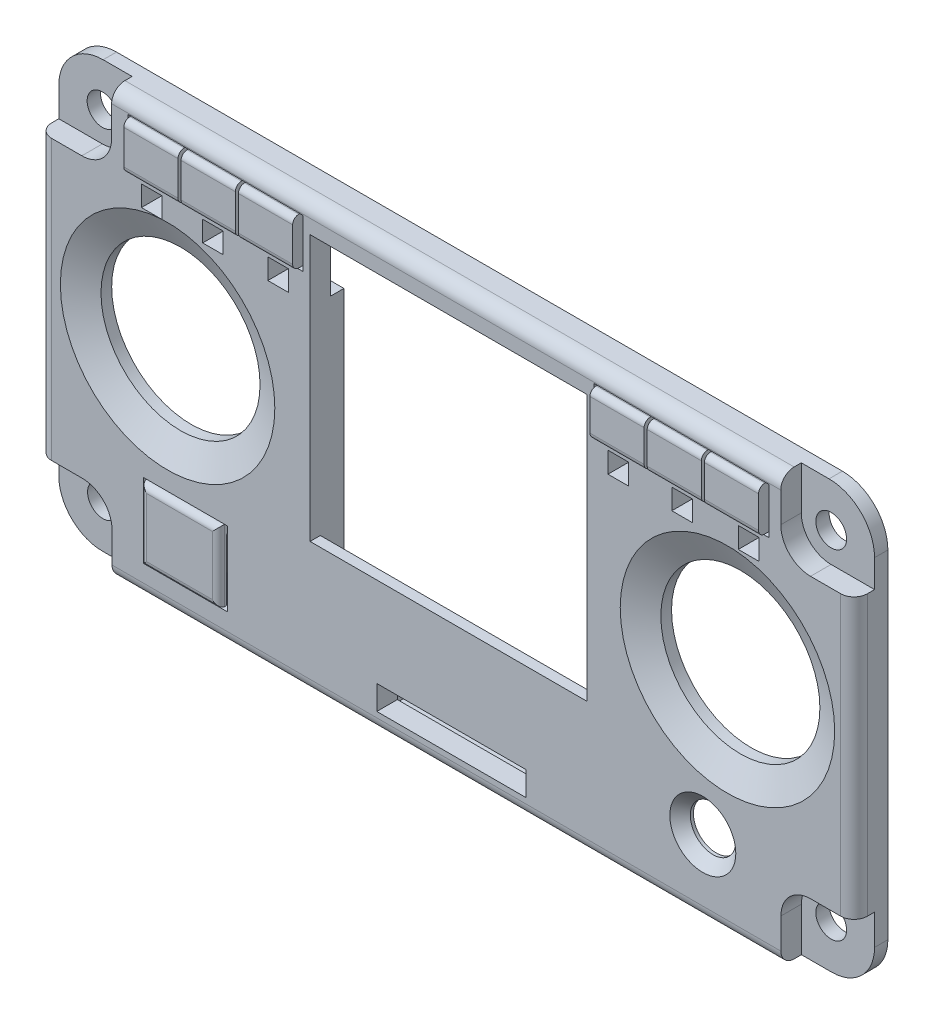
SolidWorks part; units mm, degrees
ref_plane "前视基准面" through (0, 0, 0) normal (0, 0, 1) x (1, 0, 0)
ref_plane "上视基准面" through (0, 0, 0) normal (0, 1, 0) x (1, 0, 0)
ref_plane "右视基准面" through (0, 0, 0) normal (1, 0, 0) x (0, 0, -1)
other "Configuration Table"
sketch "草图2" plane through (0, 0, 0) normal (0, 0, 1) x (1, 0, 0)
  line L0 (-0.1298, 2.7305) -> (-0.1298, 35.6715) construction
  line L1 (2.794, 39.9954) -> (73.5331, 39.9954)
  line L2 (-1.5298, 35.6715) -> (-1.5298, 2.7305)
  line L3 (2.715, -1.5143) -> (73.7871, -1.5143)
  line L4 (77.9685, 35.5601) -> (77.9685, 2.667)
  line L5 (76.5685, 35.5601) -> (76.5685, 2.667) construction
  line L6 (73.7871, -0.1143) -> (2.715, -0.1143) construction
  line L8 (2.794, 38.5954) -> (73.5331, 38.5954) construction
  line L9 (2.794, 38.5954) -> (2.794, 39.9954) construction
  line L10 (-0.1298, 35.6715) -> (-1.5298, 35.6715) construction
  line L11 (-0.1298, 2.7305) -> (-1.5298, 2.7305) construction
  line L12 (2.715, -0.1143) -> (2.715, -1.5143) construction
  line L13 (73.7871, -0.1143) -> (73.7871, -1.5143) construction
  line L14 (76.5685, 2.667) -> (77.9685, 2.667) construction
  line L15 (76.584, 35.5601) -> (77.9685, 35.5601) construction
  line L16 (73.5331, 38.5954) -> (73.5331, 39.9954) construction
  line L17 (30.5641, 3.583) -> (52.3741, 3.583) construction
  line L18 (6.2018, 38.5954) -> (24.9583, 38.5954)
  line L19 (6.2018, 38.5954) -> (6.2018, 31.1287)
  line L20 (6.2018, 31.1287) -> (24.9583, 31.1287)
  line L22 (70.5505, 38.5954) -> (52.3741, 38.5954)
  line L23 (70.5505, 38.5954) -> (70.5505, 31.0419)
  line L24 (70.5505, 31.0419) -> (52.3741, 31.0419)
  line L26 (31.2431, 3.583) -> (46.4779, 3.583)
  line L27 (31.2431, 3.583) -> (31.2431, -0.1143)
  line L28 (31.2431, -0.1143) -> (46.4779, -0.1143)
  line L29 (46.4779, 3.583) -> (46.4779, -0.1143)
  line L30 (14.927, 4.0945) -> (14.927, 6.0655) construction
  line L31 (8.727, 8.705) -> (16.927, 8.705)
  line L32 (8.727, 8.705) -> (8.727, 1.455)
  line L33 (8.727, 1.455) -> (16.927, 1.455)
  line L34 (16.927, 8.705) -> (16.927, 1.455)
  line L35 (11.3621, 3.455) -> (14.2919, 3.455) construction
  line L36 (14.2919, 6.705) -> (11.3621, 6.705) construction
  line L37 (10.727, 6.0655) -> (10.727, 4.0945) construction
  line L38 (52.3741, 3.583) -> (52.3741, 6.583) construction
  line L40 (24.9583, 31.1287) -> (24.9583, 5.083)
  line L41 (24.9583, 5.083) -> (52.3741, 5.083)
  line L42 (52.3741, 31.0419) -> (52.3741, 5.083)
  line L43 (52.3741, 38.5954) -> (24.9583, 38.5954)
  line L44 (63.2323, 5.8356) -> (69.3364, 5.8356) construction
  line L45 (63.2323, 5.8356) -> (63.2323, 11.3554) construction
  line L46 (68.7595, 7.7533) -> (68.7595, 3.9307)
  line L47 (68.7595, 3.9307) -> (65.2353, 0.4066)
  line L48 (66.3957, 0.4066) -> (58.3361, 0.4066) construction
  line L49 (65.2353, 0.4066) -> (61.2569, 0.4066)
  line L50 (61.2569, 0.4066) -> (57.7328, 3.9307)
  line L51 (57.7328, 3.9307) -> (57.7328, 7.4704)
  line L52 (57.7328, 7.4704) -> (61.6177, 11.3554)
  line L53 (61.6177, 11.3554) -> (65.1574, 11.3554)
  line L54 (65.1574, 11.3554) -> (68.7595, 7.7533)
  line L55 (59.557, 4.2278) -> (61.6319, 2.1529) construction
  line L56 (67.2181, 4.5106) -> (64.5775, 1.8701) construction
  line L57 (64.8603, 9.5311) -> (66.9352, 7.4562) construction
  line L58 (59.4863, 7.1027) -> (61.9855, 9.6018) construction
  line L59 (63.9532, 10.1554) -> (62.539, 10.1554) construction
  line L60 (67.5595, 5.1349) -> (67.5595, 6.5491) construction
  line L61 (58.9328, 6.5491) -> (58.9328, 5.1349) construction
  circle A2 centre (2.7754, 2.755) radius 1.5 construction
  circle A3 centre (2.7754, 2.755) radius 1.5
  circle A4 centre (73.7448, 2.755) radius 1.5 construction
  circle A5 centre (73.7448, 2.755) radius 1.5
  circle A6 centre (73.7448, 35.7671) radius 1.5 construction
  circle A7 centre (73.7448, 35.7671) radius 1.5
  circle A8 centre (2.7305, 35.7506) radius 1.5 construction
  circle A9 centre (2.7305, 35.7506) radius 1.5
  circle A10 centre (65.6341, 20.9531) radius 7.75
  circle A11 centre (11.074, 20.953) radius 7.75
  arc A12 (2.794, 39.9954) -> (-1.5298, 35.6715) centre (2.794, 35.6715) ccw
  arc A13 (73.5331, 39.9954) -> (77.9685, 35.5601) centre (73.5331, 35.5601) cw
  arc A14 (77.9685, 2.667) -> (73.7871, -1.5143) centre (73.7871, 2.667) cw
  arc A15 (-1.5298, 2.7305) -> (2.715, -1.5143) centre (2.715, 2.7305) ccw
  dimension "D1" = 1.4
  dimension "D9" = 15.5
  dimension "D10" = 15.5
  dimension "D2" = 1.4
  dimension "D3" = 1.4
  dimension "D4" = 1.4
  dimension "D5" = 2
  dimension "D6" = 2
  dimension "D7" = 2
  dimension "D8" = 2
  dimension "D11" = 1.5
  dimension "D12" = 1.5
  dimension "D13" = 1.5
  dimension "D14" = 1.5
  dimension "D15" = 1.2
  dimension "D16" = 1.2
  dimension "D17" = 1.2
extrude "凸台-拉伸1" add sketch "草图2" along normal blind 1.3
sketch "草图3" plane through (0, 0, 1.3) normal (0, 0, 1) x (1, 0, 0)
  line L0 (5.615, 35.7506) -> (5.615, 39.9954)
  line L1 (73.5331, 39.9954) -> (2.794, 39.9954) construction
  line L2 (5.615, 39.9954) -> (70.8292, 39.9954)
  line L3 (70.8292, 39.9954) -> (70.8292, 35.7671)
  line L4 (73.7292, 32.8671) -> (77.9685, 32.8671)
  line L5 (77.9685, 2.667) -> (77.9685, 35.5601) construction
  line L6 (77.9685, 32.8671) -> (77.9685, 5.6489)
  line L7 (77.9685, 5.6489) -> (73.7448, 5.655)
  line L8 (70.8448, 2.755) -> (70.8448, -1.5143)
  line L9 (2.715, -1.5143) -> (73.7871, -1.5143) construction
  line L10 (70.8448, -1.5143) -> (5.6599, -1.5143)
  line L11 (5.6599, -1.5143) -> (5.6599, 2.755)
  line L12 (2.7599, 5.655) -> (-1.5298, 5.655)
  line L13 (-1.5298, 35.6715) -> (-1.5298, 2.7305) construction
  line L14 (-1.5298, 5.655) -> (-1.5298, 32.8506)
  line L15 (-1.5298, 32.8506) -> (2.715, 32.8506)
  line L16 (70.5505, 38.5954) -> (6.2018, 38.5954) construction
  line L17 (7.2014, 38.5954) -> (24.2583, 38.5954)
  line L18 (7.2014, 38.5954) -> (7.2014, 33.8601)
  line L19 (7.2014, 33.8601) -> (24.2583, 33.8601)
  line L20 (24.2583, 38.5954) -> (24.2583, 33.8601)
  line L22 (52.6355, 38.5954) -> (69.6656, 38.5954)
  line L23 (52.6355, 38.5954) -> (52.6355, 34.1025)
  line L24 (52.6355, 34.1025) -> (69.6656, 34.1025)
  line L25 (69.6656, 38.5954) -> (69.6656, 34.1025)
  line L26 (24.9583, 37.3191) -> (51.9355, 37.3191)
  line L27 (24.9583, 37.3191) -> (24.9583, 6.9225)
  line L28 (24.9583, 6.9225) -> (51.9355, 6.9225)
  line L29 (51.9355, 37.3191) -> (51.9355, 6.9225)
  line L30 (24.9583, 31.1287) -> (24.9583, 5.083) construction
  line L32 (31.4629, 2.6894) -> (46.0176, 2.6894)
  line L33 (31.4629, 2.6894) -> (31.4629, 0.3259)
  line L34 (31.4629, 0.3259) -> (46.0176, 0.3259)
  line L35 (46.0176, 2.6894) -> (46.0176, 0.3259)
  circle A0 centre (2.715, 35.7506) radius 2.9 construction
  circle A1 centre (2.7599, 2.755) radius 2.9 construction
  circle A2 centre (73.7448, 2.755) radius 2.9 construction
  circle A3 centre (73.7292, 35.7671) radius 2.9 construction
  arc A4 (70.8292, 35.7671) -> (73.7292, 32.8671) centre (73.7292, 35.7671) ccw
  arc A5 (73.7448, 5.655) -> (70.8448, 2.755) centre (73.7406, 2.7592) ccw
  arc A6 (5.6599, 2.755) -> (2.7599, 5.655) centre (2.7599, 2.755) ccw
  arc A7 (2.715, 32.8506) -> (5.615, 35.7506) centre (2.715, 35.7506) ccw
  circle A8 centre (63.2323, 5.8356) radius 2.2156
  circle A9 centre (65.6341, 20.9531) radius 7.75
  circle A10 centre (11.074, 20.953) radius 7.75
  spline S0 degree 2 poles (69.6661, 34.1141) (69.6661, 34.0618) (69.6289, 34.0243) (69.592, 33.9871) (69.5391, 33.9871) knots 0 0 0 0.5 0.5 1 1 1 construction
  dimension "D1" = 5.8
  dimension "D2" = 5.8
  dimension "D3" = 5.8
  dimension "D4" = 5.8
  dimension "D5" = 0.7
  dimension "D6" = 0.7
extrude "凸台-拉伸2" add sketch "草图3" along normal blind 2
chamfer "倒角1" distance 2.7 angle 25 2 edges at (73.3841, 20.9531, 3.3) (18.824, 20.953, 3.3) first distance on face at (73.3841, 20.9531, 3.3)
chamfer "倒角2" distance 1 angle 45 1 edges at (65.4479, 5.8356, 3.3)
fillet "圆角1" radius 1.3 4 edges at (77.9685, 19.258, 3.3) (38.2221, 39.9954, 3.3) (-1.5298, 19.2528, 3.3) (38.2523, -1.5143, 3.3)
sketch "草图4" plane through (0, 0, 0) normal (0, 0, -1) x (-1, 0, 0)
  line L1 (-68.6912, 33.6392) -> (-66.6911, 33.6392)
  line L2 (-68.6912, 33.6392) -> (-68.6912, 31.6151)
  line L3 (-68.6912, 31.6151) -> (-66.6911, 31.6151)
  line L4 (-66.6911, 33.6392) -> (-66.6911, 31.6151)
  line L5 (-62.2141, 33.6392) -> (-60.2141, 33.6392)
  line L6 (-62.2141, 33.6392) -> (-62.2141, 31.6392)
  line L7 (-62.2141, 31.6392) -> (-60.2141, 31.6392)
  line L8 (-60.2141, 33.6392) -> (-60.2141, 31.6392)
  line L9 (-55.9911, 33.6392) -> (-53.9911, 33.6392)
  line L10 (-55.9911, 33.6392) -> (-55.9911, 31.6151)
  line L11 (-55.9911, 31.6151) -> (-53.9911, 31.6151)
  line L12 (-53.9911, 33.6392) -> (-53.9911, 31.6151)
  line L13 (-22.8441, 33.3852) -> (-20.8441, 33.3852)
  line L14 (-22.8441, 33.3852) -> (-22.8441, 31.3852)
  line L15 (-22.8441, 31.3852) -> (-20.8441, 31.3852)
  line L16 (-20.8441, 33.3852) -> (-20.8441, 31.3852)
  line L17 (-16.4941, 33.3852) -> (-14.4941, 33.3852)
  line L18 (-16.4941, 33.3852) -> (-16.4941, 31.3852)
  line L19 (-16.4941, 31.3852) -> (-14.4941, 31.3852)
  line L20 (-14.4941, 33.3852) -> (-14.4941, 31.3852)
  line L21 (-10.525, 33.3852) -> (-8.525, 33.3852)
  line L22 (-10.525, 33.3852) -> (-10.525, 31.3852)
  line L23 (-10.525, 31.3852) -> (-8.525, 31.3852)
  line L24 (-8.525, 33.3852) -> (-8.525, 31.3852)
extrude "切除-拉伸1" cut sketch "草图4" against normal up to surface (3.3 mm away) up to face at (66.4479, 5.8356, 3.3)
sketch "草图5" plane through (0, 0, 3.3) normal (0, 0, 1) x (1, 0, 0)
  line L0 (24.2583, 38.5954) -> (7.2014, 38.5954) construction
  line L1 (7.5014, 38.5954) -> (12.7871, 38.5954)
  line L2 (7.5014, 38.5954) -> (7.5014, 34.0601)
  line L3 (7.5014, 34.0601) -> (12.7871, 34.0601)
  line L4 (12.7871, 38.5954) -> (12.7871, 34.0601)
  line L5 (69.6656, 38.5954) -> (52.6355, 38.5954) construction
  line L6 (13.0871, 38.5954) -> (18.3727, 38.5954)
  line L7 (13.0871, 38.5954) -> (13.0871, 34.0601)
  line L8 (13.0871, 34.0601) -> (18.3727, 34.0601)
  line L9 (18.3727, 38.5954) -> (18.3727, 34.0601)
  line L10 (18.6727, 38.5954) -> (23.9583, 38.5954)
  line L11 (18.6727, 38.5954) -> (18.6727, 34.0601)
  line L12 (18.6727, 34.0601) -> (23.9583, 34.0601)
  line L13 (23.9583, 38.5954) -> (23.9583, 34.0601)
  line L14 (52.9355, 38.5954) -> (58.2122, 38.5954)
  line L15 (52.9355, 38.5954) -> (52.9355, 34.3025)
  line L16 (52.9355, 34.3025) -> (58.2122, 34.3025)
  line L17 (58.2122, 38.5954) -> (58.2122, 34.3025)
  line L18 (7.2014, 38.5954) -> (7.2014, 33.8601) construction
  line L19 (58.5122, 38.5954) -> (63.7889, 38.5954)
  line L20 (58.5122, 38.5954) -> (58.5122, 34.3025)
  line L21 (58.5122, 34.3025) -> (63.7889, 34.3025)
  line L22 (63.7889, 38.5954) -> (63.7889, 34.3025)
  line L23 (64.0889, 38.5954) -> (69.3656, 38.5954)
  line L24 (64.0889, 38.5954) -> (64.0889, 34.3025)
  line L25 (64.0889, 34.3025) -> (69.3656, 34.3025)
  line L26 (69.3656, 38.5954) -> (69.3656, 34.3025)
  line L27 (7.2014, 33.8601) -> (24.2583, 33.8601) construction
  line L28 (24.2583, 33.8601) -> (24.2583, 38.5954) construction
  line L29 (52.6355, 38.5954) -> (52.6355, 34.1025) construction
  line L30 (69.6656, 34.1025) -> (69.6656, 38.5954) construction
  line L31 (52.6355, 34.1025) -> (69.6656, 34.1025) construction
  dimension "D1" = 0.3
  dimension "D2" = 0.3
  dimension "D3" = 0.3
  dimension "D4" = 0.2
  dimension "D5" = 0.3
  dimension "D6" = 0.3
  dimension "D7" = 0.3
  dimension "D8" = 0.3
  dimension "D9" = 0.3
  dimension "D10" = 0.2
extrude "凸台-拉伸3" add sketch "草图5" against normal blind 0.3
sketch "草图6" plane through (0, 0, 3) normal (0, 0, -1) x (-1, 0, 0)
  circle A0 centre (-9.3961, 35.56) radius 1.4999
  circle A1 centre (-15.6961, 35.56) radius 1.4999
  circle A2 centre (-21.9961, 35.56) radius 1.4999
  circle A3 centre (-54.8391, 35.814) radius 1.5116
  circle A4 centre (-61.1391, 35.814) radius 1.5116
  circle A5 centre (-67.439, 35.814) radius 1.5116
extrude "凸台-拉伸4" add sketch "草图6" along normal blind 0.4
sketch "草图7" plane through (0, 0, 3.3) normal (0, 0, 1) x (1, 0, 0)
  line L1 (12.7871, 38.5954) -> (7.5014, 38.5954)
  line L2 (12.7871, 38.5954) -> (12.7871, 34.0601)
  line L3 (12.7871, 34.0601) -> (7.5014, 34.0601)
  line L4 (7.5014, 38.5954) -> (7.5014, 34.0601)
  line L5 (13.0871, 34.0601) -> (18.3727, 34.0601)
  line L6 (13.0871, 34.0601) -> (13.0871, 38.5954)
  line L7 (13.0871, 38.5954) -> (18.3727, 38.5954)
  line L8 (18.3727, 34.0601) -> (18.3727, 38.5954)
  line L9 (18.6727, 34.0601) -> (23.9583, 34.0601)
  line L10 (18.6727, 34.0601) -> (18.6727, 38.5954)
  line L11 (18.6727, 38.5954) -> (23.9583, 38.5954)
  line L12 (23.9583, 34.0601) -> (23.9583, 38.5954)
  line L13 (52.9355, 34.3025) -> (58.2122, 34.3025)
  line L14 (52.9355, 34.3025) -> (52.9355, 38.5954)
  line L15 (52.9355, 38.5954) -> (58.2122, 38.5954)
  line L16 (58.2122, 34.3025) -> (58.2122, 38.5954)
  line L17 (58.5122, 34.3025) -> (63.7889, 34.3025)
  line L18 (58.5122, 34.3025) -> (58.5122, 38.5954)
  line L19 (58.5122, 38.5954) -> (63.7889, 38.5954)
  line L20 (63.7889, 34.3025) -> (63.7889, 38.5954)
  line L21 (64.0889, 34.3025) -> (69.3656, 34.3025)
  line L22 (64.0889, 34.3025) -> (64.0889, 38.5954)
  line L23 (64.0889, 38.5954) -> (69.3656, 38.5954)
  line L24 (69.3656, 34.3025) -> (69.3656, 38.5954)
extrude "凸台-拉伸5" add sketch "草图7" along normal blind 0.7
fillet "圆角2" radius 0.6 12 edges at (55.5739, 34.3025, 4) (61.1506, 34.3025, 4) (66.7273, 34.3025, 4) (66.7273, 38.5954, 4) (61.1506, 38.5954, 4) (55.5739, 38.5954, 4) (21.3155, 38.5954, 4) (21.3155, 34.0601, 4) (15.7299, 34.0601, 4) (15.7299, 38.5954, 4) (10.1442, 38.5954, 4) (10.1442, 34.0601, 4)
sketch "草图8" plane through (0, 0, 1.3) normal (0, 0, -1) x (-1, 0, 0)
  line L1 (-16.927, 1.455) -> (-8.727, 1.455)
  line L2 (-16.927, 1.455) -> (-16.927, 8.705)
  line L3 (-16.927, 8.705) -> (-8.727, 8.705)
  line L4 (-8.727, 1.455) -> (-8.727, 8.705)
extrude "切除-拉伸2" cut sketch "草图8" against normal up to surface (2 mm away) up to face at (67.6911, 32.6271, 3.3)
sketch "草图9" plane through (0, 0, 3.3) normal (0, 0, 1) x (1, 0, 0)
  line L0 (8.727, 8.705) -> (16.927, 8.705) construction
  line L1 (9.027, 8.705) -> (16.627, 8.705)
  line L2 (9.027, 8.705) -> (9.027, 1.755)
  line L3 (9.027, 1.755) -> (16.627, 1.755)
  line L4 (16.627, 8.705) -> (16.627, 1.755)
  line L5 (16.927, 1.455) -> (8.727, 1.455) construction
  line L6 (16.927, 8.705) -> (16.927, 1.455) construction
  line L7 (8.727, 1.455) -> (8.727, 8.705) construction
  dimension "D1" = 0.3
  dimension "D2" = 0.3
  dimension "D3" = 0.3
extrude "凸台-拉伸6" add sketch "草图9" against normal blind 0.2
sketch "草图11" plane through (0, 0, 3.3) normal (0, 0, 1) x (1, 0, 0)
  line L1 (9.027, 1.755) -> (16.627, 1.755)
  line L2 (9.027, 1.755) -> (9.027, 8.705)
  line L3 (9.027, 8.705) -> (16.627, 8.705)
  line L4 (16.627, 1.755) -> (16.627, 8.705)
extrude "凸台-拉伸8" add sketch "草图11" along normal blind 0.6
fillet "圆角3" radius 0.6 4 edges at (16.627, 5.23, 3.9) (12.827, 1.755, 3.9) (9.027, 5.23, 3.9) (12.827, 8.705, 3.9)
chamfer "倒角3" distance 0.6 angle 45 6 edges at (66.7273, 38.5954, 3) (61.1506, 38.5954, 3) (55.5739, 38.5954, 3) (21.3155, 38.5954, 3) (15.7299, 38.5954, 3) (10.1442, 38.5954, 3)
sketch "草图12" plane through (0, 0, 1.3) normal (0, 0, -1) x (-1, 0, 0)
  line L8 (-68.7595, 7.7533) -> (-65.1574, 11.3554) construction
  line L9 (-68.7595, 3.9307) -> (-68.7595, 7.7533) construction
  line L10 (-65.2353, 0.4066) -> (-68.7595, 3.9307) construction
  line L11 (-61.2569, 0.4066) -> (-65.2353, 0.4066) construction
  line L12 (-57.7328, 3.9307) -> (-61.2569, 0.4066) construction
  line L13 (-57.7328, 7.4704) -> (-57.7328, 3.9307) construction
  line L14 (-61.6177, 11.3554) -> (-57.7328, 7.4704) construction
  line L15 (-65.1574, 11.3554) -> (-61.6177, 11.3554) construction
  line L16 (-68.7595, 7.7533) -> (-65.1574, 11.3554)
  line L17 (-68.7595, 3.9307) -> (-68.7595, 7.7533)
  line L18 (-65.2353, 0.4066) -> (-68.7595, 3.9307)
  line L19 (-61.2569, 0.4066) -> (-65.2353, 0.4066)
  line L20 (-57.7328, 3.9307) -> (-61.2569, 0.4066)
  line L21 (-57.7328, 7.4704) -> (-57.7328, 3.9307)
  line L22 (-61.6177, 11.3554) -> (-57.7328, 7.4704)
  line L23 (-65.1574, 11.3554) -> (-61.6177, 11.3554)
extrude "切除-拉伸3" cut sketch "草图12" against normal blind 0.7
chamfer "倒角4" distance 1 angle 40 1 edges at (12.827, 8.705, 3.1) first distance on face at (12.827, 5.23, 3.1)
sketch "草图13" plane through (0, 0, 0) normal (0, 0, -1) x (-1, 0, 0)
  line L1 (-75.3341, 30.0531) -> (-55.9341, 30.0531)
  line L2 (-75.3341, 30.0531) -> (-75.3341, 11.6031)
  line L3 (-75.3341, 11.6031) -> (-55.9341, 11.6031)
  line L4 (-55.9341, 30.0531) -> (-55.9341, 11.6031)
  line L5 (-20.774, 30.053) -> (-1.374, 30.053)
  line L6 (-20.774, 30.053) -> (-20.774, 11.603)
  line L7 (-20.774, 11.603) -> (-1.374, 11.603)
  line L8 (-1.374, 30.053) -> (-1.374, 11.603)
  line L12 (-20.274, 29.803) -> (-1.874, 29.803) construction
  line L13 (-20.274, 29.803) -> (-20.274, 12.103) construction
  line L14 (-20.274, 12.103) -> (-1.874, 12.103) construction
  line L15 (-1.874, 29.803) -> (-1.874, 12.103) construction
  line L16 (-74.8341, 29.8031) -> (-56.4341, 29.8031) construction
  line L17 (-74.8341, 29.8031) -> (-74.8341, 12.1031) construction
  line L18 (-74.8341, 12.1031) -> (-56.4341, 12.1031) construction
  line L19 (-56.4341, 29.8031) -> (-56.4341, 12.1031) construction
  dimension "D1" = 0.5
  dimension "D2" = 0.5
  dimension "D3" = 0.5
  dimension "D4" = 0.5
  dimension "D5" = 0.5
  dimension "D6" = 0.5
  dimension "D7" = 0.5
  dimension "D8" = 0.5
extrude "切除-拉伸4" cut sketch "草图13" against normal blind 1
sketch "草图14" plane through (0, 0, 3.3) normal (0, 0, 1) x (1, 0, 0)
  line L0 (51.9355, 6.9225) -> (51.9355, 37.3191) construction
  line L1 (24.9583, 6.9225) -> (51.9355, 6.9225)
  line L2 (24.9583, 6.9225) -> (24.9583, 11.4225)
  line L3 (24.9583, 11.4225) -> (51.9355, 11.4225)
  line L4 (51.9355, 6.9225) -> (51.9355, 11.4225)
  dimension "D1" = 4.5
extrude "凸台-拉伸9" add sketch "草图14" against normal blind 1
sketch "草图15" plane through (0, 0, 3.1) normal (0, 0, -1) x (-1, 0, 0)
  circle A0 centre (-12.9782, 4.6943) radius 1.5
  dimension "D1" = 3
extrude "凸台-拉伸10" add sketch "草图15" along normal blind 1.3
sketch "草图16" plane through (0, 0, 1.8) normal (0, 0, -1) x (-1, 0, 0)
  circle A0 centre (-12.9782, 4.6943) radius 1.5
extrude "切除-拉伸5" cut sketch "草图16" against normal blind 0.8
